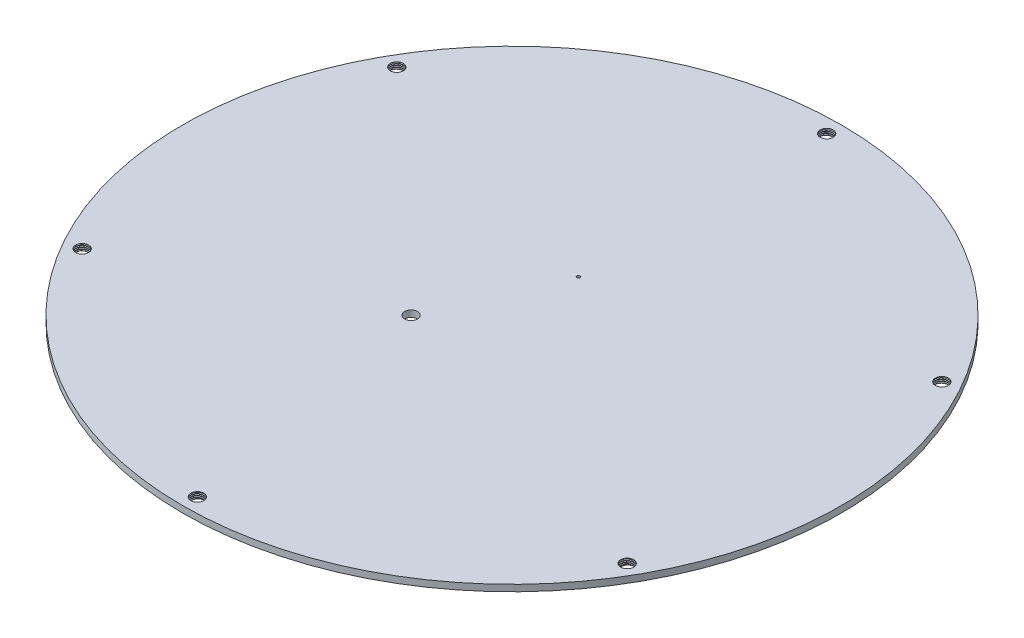
SolidWorks part; units mm, degrees
material "1060 Alloy"
ref_plane "Front Plane" through (0, 0, 0) normal (0, 0, 1) x (1, 0, 0)
ref_plane "Top Plane" through (0, 0, 0) normal (0, 1, 0) x (1, 0, 0)
ref_plane "Right Plane" through (0, 0, 0) normal (1, 0, 0) x (0, 0, -1)
sketch "Sketch1" plane through (0, 0, 0) normal (0, 1, 0) x (1, 0, 0)
  circle A0 centre (0, 0) radius 50.8
  circle A1 centre (0, 48.5) radius 1
  circle A2 centre (42.0022, 24.25) radius 1
  circle A3 centre (42.0022, -24.25) radius 1
  circle A4 centre (0, -48.5) radius 1
  circle A5 centre (-42.0022, -24.25) radius 1
  circle A6 centre (-42.0022, 24.25) radius 1
  point P17 (0, 0)
  dimension "D1" = 101.6
  dimension "D2" = 2
  dimension "D3" = 48.5
  dimension "D4" = 6
extrude "Boss-Extrude1" add sketch "Sketch1" along normal blind 1
thread "Thread1" pitch 0.25 method cut profile "Thread Profile1" start angle 0, offset 0, length 10, pitch 0.25, diameter 2
ref_plane "Plane1" through (-43.0022, 1, 24.25) normal (0, 0, 1) x (-1, 0, 0)
sketch "Thread Profile1" plane through (-43.0022, 1, 24.25) normal (0, 0, 1) x (-1, 0, 0)
  line L0 (0, 0) -> (0, 0.25) construction
  line L1 (0, 0) -> (0.1353, 0.0781)
  line L2 (0.1353, 0.0781) -> (0.1353, 0.1094)
  line L3 (0.1353, 0.1094) -> (0, 0.1875)
  line L4 (0.1353, 0.0937) -> (0, 0.0937) construction
  line L11 (0, 0) -> (0, 0.1875)
  point P2 (0, 0)
  dimension "Pitch" = 0.25
  dimension "Profile_Angle" = 60
  dimension "Profile_Land" = 0.0312
  dimension "Profile_Height" = 0.1353
pattern_circular "CirPattern1" count 6 over 360 about axis through (0, 0, 0) along (0, 1, 0) of "Thread1"
sketch "Sketch2" plane through (0, 1, 0) normal (0, 1, 0) x (1, 0, 0)
  line L0 (0, 0) -> (0, 10.25) construction
  line L1 (0, 10.25) -> (0, 0) construction
  line L2 (0, 0) -> (-20.5223, -20.5223) construction
  circle A0 centre (0, 10.25) radius 0.25
  circle A1 centre (-7.7782, -7.7782) radius 1
  dimension "D1" = 0.5
  dimension "D3" = 2
  dimension "D2" = 10.25
  dimension "D4" = 11
extrude "Cut-Extrude1" cut sketch "Sketch2" against normal through all both and the other way through all
